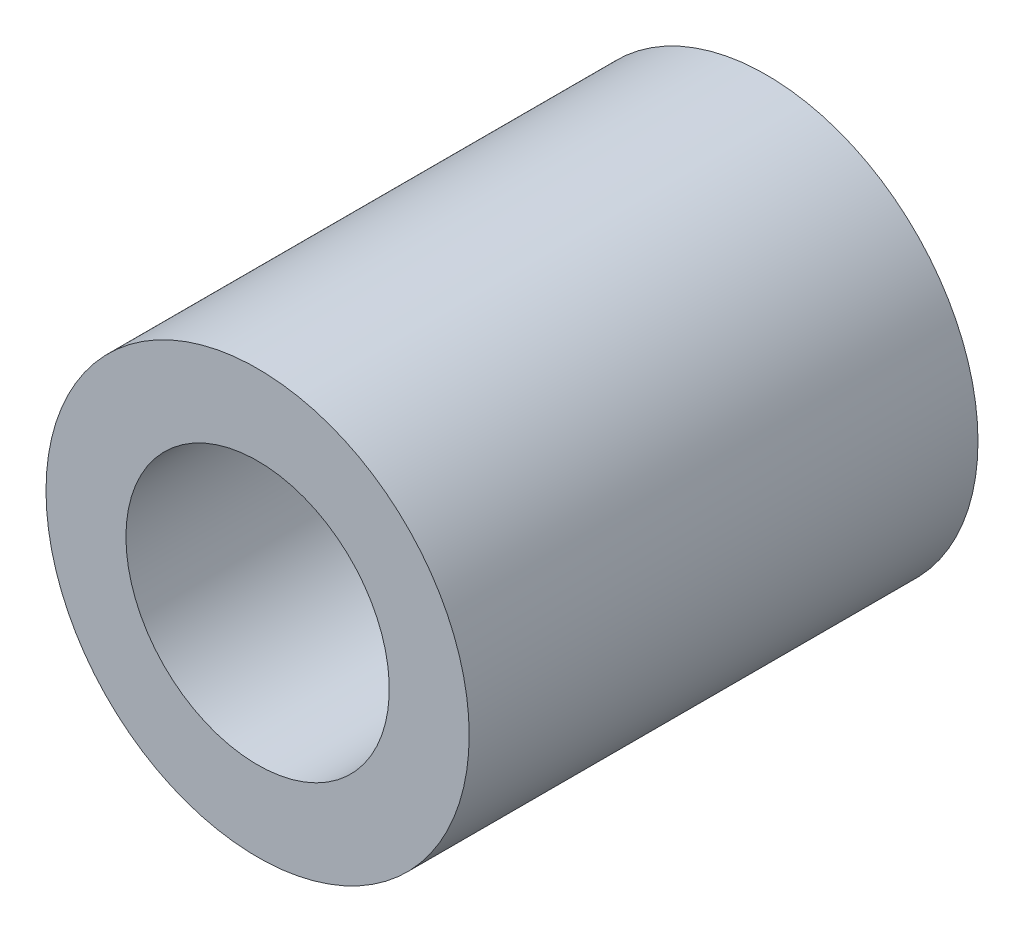
SolidWorks part; units mm, degrees
material "7075-T6 (SN)"
ref_plane "Front Plane" through (0, 0, 0) normal (0, 0, 1) x (1, 0, 0)
ref_plane "Top Plane" through (0, 0, 0) normal (0, 1, 0) x (1, 0, 0)
ref_plane "Right Plane" through (0, 0, 0) normal (1, 0, 0) x (0, 0, -1)
ref_axis "Centre Axis" through (0, 0, -0.3585) along (0, 0, 1)
sketch "Sketch1" plane through (0, 0, 0) normal (0, 0, 1) x (1, 0, 0)
  circle A1 centre (0, 0) radius 4
  dimension "D1" = 8
extrude "Boss-Extrude1" add sketch "Sketch1" along normal blind 9.6188
hole_wizard "#10 Clearance Hole1" positions "Sketch2" profile "Sketch4" hole size "#10" standard "ANSI Inch" end condition through all
sketch "Sketch2" plane through (0, 0, 0) normal (0, 0, -1) x (-1, 0, 0)
  point P0 (0, 0)
sketch "Sketch4" plane through (0, 0, 0) normal (1, 0, 0) x (0, 1, 0)
  line L0 (0, 0) -> (0, 9.6188)
  line L1 (0, 9.6188) -> (2.4892, 9.6188)
  line L2 (2.4892, 9.6188) -> (2.4892, 0)
  line L5 (2.4892, 0) -> (0, 0)
  line L11 (0, -6.35) -> (0, 107.95) construction
  dimension "Thru Hole Dia." = 4.9784
  dimension "Thru Hole Depth" = 9.6188
